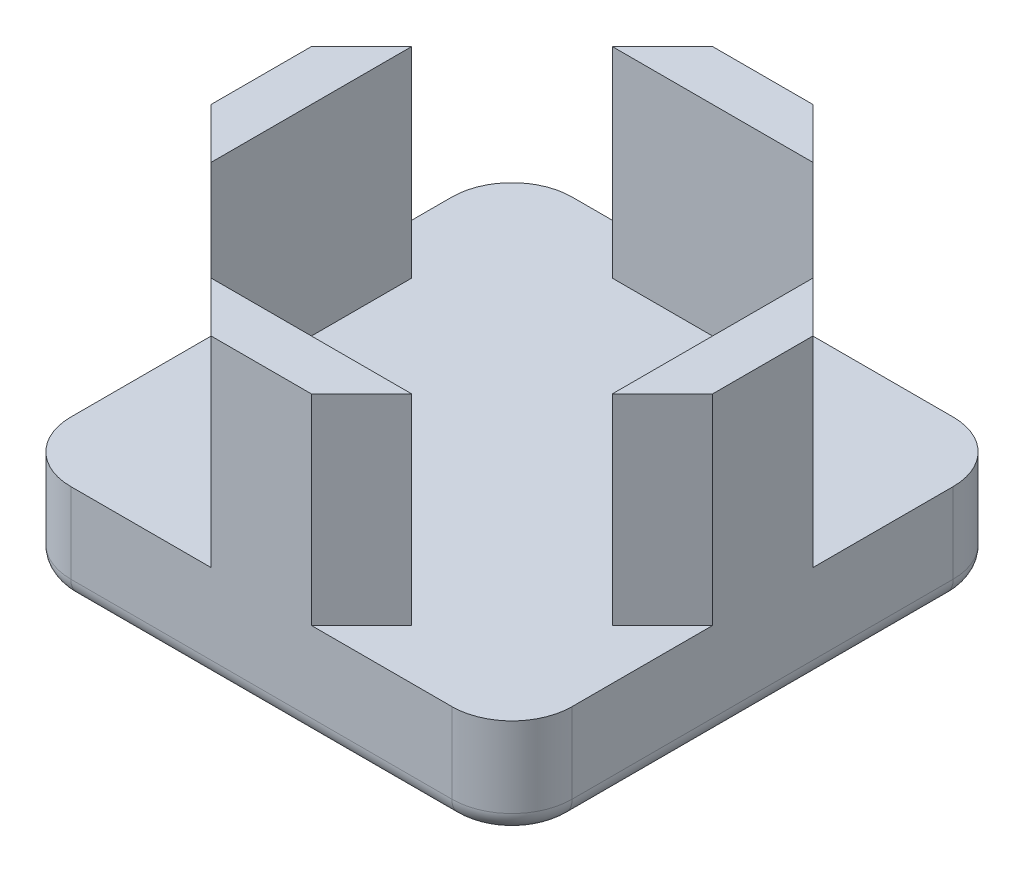
SolidWorks part; units mm, degrees
ref_plane "Front Plane" through (0, 0, 0) normal (0, 0, 1) x (1, 0, 0)
ref_plane "Top Plane" through (0, 0, 0) normal (0, 1, 0) x (1, 0, 0)
ref_plane "Right Plane" through (0, 0, 0) normal (1, 0, 0) x (0, 0, -1)
sketch "Sketch3" plane through (0, 0, 0) normal (0, 1, 0) x (1, 0, 0)
  line L0 (-12.5, 0) -> (12.5, 0) construction
  line L5 (-9.5, 12.5) -> (-2.5, 12.5)
  line L6 (0, -12.5) -> (0, 12.5) construction
  line L11 (-2.5, 12.5) -> (2.5, 12.5)
  line L12 (2.5, 12.5) -> (9.5, 12.5)
  line L13 (12.5, 9.5) -> (12.5, 2.5)
  line L14 (12.5, 2.5) -> (12.5, -2.5)
  line L15 (12.5, -2.5) -> (12.5, -9.5)
  line L16 (9.5, -12.5) -> (2.5, -12.5)
  line L17 (2.5, -12.5) -> (-2.5, -12.5)
  line L18 (-2.5, -12.5) -> (-9.5, -12.5)
  line L19 (-12.5, -9.5) -> (-12.5, -2.5)
  line L20 (-12.5, -2.5) -> (-12.5, 2.5)
  line L21 (-12.5, 2.5) -> (-12.5, 9.5)
  line L22 (-12.5, -2.5) -> (-10, -5)
  line L23 (-10, -5) -> (-10, 5)
  line L24 (-10, 5) -> (-12.5, 2.5)
  line L25 (-2.5, 12.5) -> (-5, 10)
  line L26 (-5, 10) -> (5, 10)
  line L27 (5, 10) -> (2.5, 12.5)
  line L28 (12.5, 2.5) -> (10, 5)
  line L29 (10, 5) -> (10, -5)
  line L30 (10, -5) -> (12.5, -2.5)
  line L31 (-2.5, -12.5) -> (-5, -10)
  line L32 (-5, -10) -> (5, -10)
  line L33 (5, -10) -> (2.5, -12.5)
  line L34 (-7.5, 5) -> (-5, 7.5)
  line L39 (-5, 7.5) -> (5, 7.5)
  line L40 (5, 7.5) -> (7.5, 5)
  line L41 (7.5, 5) -> (7.5, -5)
  line L42 (7.5, -5) -> (5, -7.5)
  line L43 (5, -7.5) -> (-5, -7.5)
  line L44 (-5, -7.5) -> (-7.5, -5)
  line L45 (-7.5, -5) -> (-7.5, 5)
  arc A0 (-9.5, -12.5) -> (-12.5, -9.5) centre (-9.5, -9.5) cw
  arc A1 (12.5, -9.5) -> (9.5, -12.5) centre (9.5, -9.5) cw
  arc A2 (9.5, 12.5) -> (12.5, 9.5) centre (9.5, 9.5) cw
  arc A3 (-9.5, 12.5) -> (-12.5, 9.5) centre (-9.5, 9.5) ccw
  point P2 (0, 0)
  point P6 (0, 0)
  point P26 (0, 0)
  point P39 (-7.2824, 5.6435)
  point P44 (-7.5, 0)
  point P45 (-7.1955, 5)
  point P46 (-7.4281, -5)
  point P47 (-12.5, 0)
  point P53 (-12.7916, 0.0384)
  dimension "D3" = 3
  dimension "D1" = 25
  dimension "D2" = 5
  dimension "D4" = 2.5
  dimension "D5" = 45
  dimension "D6" = 2.5
  dimension "D7" = 2.5
extrude "Boss-Extrude1" add sketch "Sketch3" along normal blind 10 contours L23 L24 L20 L22 | L26 L27 L11 L25 | L29 L30 L14 L28 | L33 L32 L31 L17 region at (0, 0, -11.1111) region at (-11.1111, 0, 0) region at (11.1111, 0, 0) region at (0, 0, 11.1111)
extrude "Boss-Extrude2" add sketch "Sketch3<4>" against normal blind 5 contours L5 A3 L21 L24 L23 L22 L19 A0 L18 L31 L32 L33 L16 A1 L15 L30 L29 L28 L13 A2 L12 L27 L26 L25 L44 L45 L34 L39 L40 L41 L42 L43 | L45 L44 L43 L42 L41 L40 L39 L34 | L33 L32 L31 L17 | L23 L24 L20 L22 | L26 L27 L11 L25 | L29 L30 L14 L28 region at (-6, 0, -12.1464) region at (0, 0, -11.1111) region at (-11.1111, 0, 0) region at (11.1111, 0, 0) region at (0, 0, 11.1111) region at (0, 0, 0)
sketch "Sketch3<4>" plane through (0, 0, 0) normal (0, 1, 0) x (1, 0, 0) same geometry as "Sketch3"
fillet "Fillet1" radius 1 8 edges at (-11.6213, -5, 11.6213) (0, -5, 12.5) (11.6213, -5, 11.6213) (12.5, -5, 0) (11.6213, -5, -11.6213) (0, -5, -12.5) (-11.6213, -5, -11.6213) (-12.5, -5, 0)
